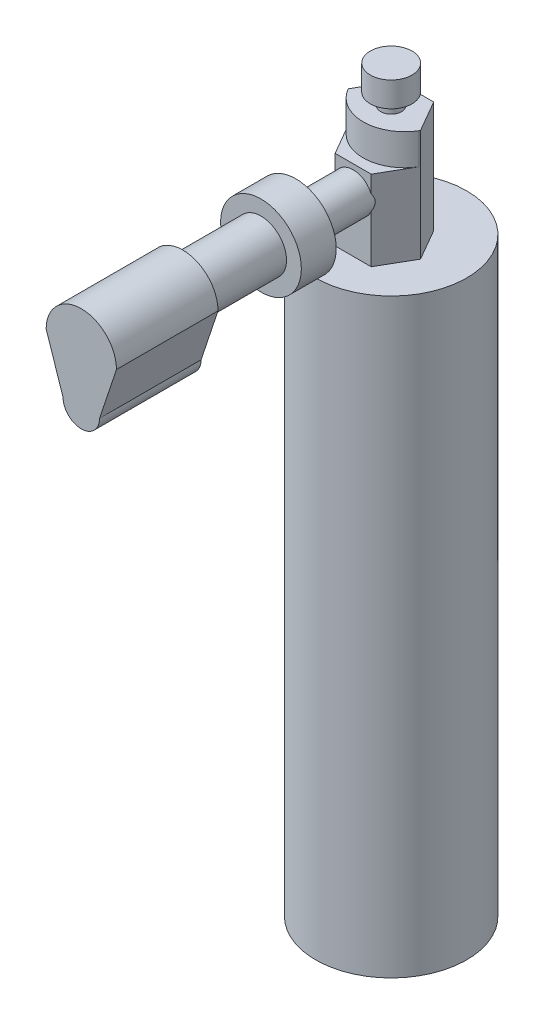
SolidWorks part; units mm, degrees
ref_plane "Front Plane" through (0, 0, 0) normal (0, 0, 1) x (1, 0, 0)
ref_plane "Top Plane" through (0, 0, 0) normal (0, 1, 0) x (1, 0, 0)
ref_plane "Right Plane" through (0, 0, 0) normal (1, 0, 0) x (0, 0, -1)
sketch "Sketch1" plane through (0, 0, 0) normal (0, 1, 0) x (1, 0, 0)
  circle A0 centre (0, 0) radius 14.5
  dimension "D1" = 29
extrude "Boss-Extrude1" add sketch "Sketch1" along normal blind 113.4
sketch "Sketch2" plane through (0, 113.4, 0) normal (0, 1, 0) x (1, 0, 0)
  circle A0 centre (0, 0) radius 2
  dimension "D1" = 4
extrude "Boss-Extrude2" add sketch "Sketch2" along normal blind 28.5
sketch "Sketch3" plane through (0, 141.9, 0) normal (0, 1, 0) x (1, 0, 0)
  circle A0 centre (0, 0) radius 4
  dimension "D1" = 8
extrude "Boss-Extrude3" add sketch "Sketch3" against normal blind 4.8
sketch "Sketch4" plane through (0, 113.4, 0) normal (0, 1, 0) x (1, 0, 0)
  line L3 (3.4641, 4.7) -> (-3.4641, 4.7)
  line L4 (-3.4641, 4.7) -> (-6.9282, -1.3)
  line L5 (-6.9282, -1.3) -> (-3.4641, -7.3)
  line L6 (-3.4641, -7.3) -> (3.4641, -7.3)
  line L7 (3.4641, -7.3) -> (6.9282, -1.3)
  line L8 (6.9282, -1.3) -> (3.4641, 4.7)
  circle A0 centre (0, 0) radius 14.5 construction
  circle A1 centre (0, -1.3) radius 6.9282 construction
  circle A4 centre (0, 0) radius 14.5 construction
  dimension "D1" = 12
  dimension "D2" = 4.7
extrude "Boss-Extrude4" add sketch "Sketch4" along normal blind 21.4
sketch "Sketch6" plane through (0, 134.8, 0) normal (0, 1, 0) x (1, 0, 0)
  line L4 (-6.9282, -1.3) -> (-6.9282, -9.4658)
  line L5 (-6.9282, -9.4658) -> (6.9282, -9.4658)
  line L6 (6.9282, -1.3) -> (6.9282, -9.4658)
  arc A0 (-6.9282, -1.3) -> (6.9282, -1.3) centre (0, 2.5618) ccw
extrude "Cut-Extrude1" cut sketch "Sketch6" against normal blind 6
sketch "Sketch7" plane through (0, 0, 7.3) normal (0, 0, 1) x (1, 0, 0)
  line L0 (-3.4641, 128.8) -> (3.4641, 128.8) construction
  circle A0 centre (0, 124.05) radius 3.75
  dimension "D1" = 7.5
  dimension "D2" = 4.75
extrude "Boss-Extrude5" add sketch "Sketch7" along normal blind 11 and the other way blind 2
sketch "Sketch8" plane through (0, 0, 18.3) normal (0, 0, 1) x (1, 0, 0)
  circle A0 centre (0, 124.05) radius 7.75
  dimension "D1" = 15.5
extrude "Boss-Extrude6" add sketch "Sketch8" along normal blind 6.7
sketch "Sketch9" plane through (0, 0, 25) normal (0, 0, 1) x (1, 0, 0)
  circle A0 centre (0, 124.05) radius 4.9
  dimension "D1" = 9.8
extrude "Boss-Extrude7" add sketch "Sketch9" along normal blind 15
sketch "Sketch10" plane through (0, 0, 40) normal (0, 0, 1) x (1, 0, 0)
  line L0 (0, 117.8) -> (0, 110.8) construction
  line L1 (-6.75, 124.05) -> (-3.5, 114.3)
  line L2 (3.5, 114.3) -> (6.75, 124.05)
  arc A0 (6.75, 124.05) -> (-6.75, 124.05) centre (0, 124.05) ccw
  arc A1 (-3.5, 114.3) -> (3.5, 114.3) centre (0, 114.3) ccw
  dimension "D1" = 13.5
  dimension "D2" = 7
extrude "Boss-Extrude8" add sketch "Sketch10" along normal blind 19.5
sketch "Sketch11" plane through (0, 141.9, 0) normal (0, 1, 0) x (1, 0, 0)
  line L0 (0, 4) -> (0.2732, 3.6147)
  line L1 (0, 4) -> (0, 3.625) construction
  line L2 (0, 4) -> (-0.2732, 3.6147)
  line L3 (0.6106, 3.9531) -> (0.8217, 3.5306)
  line L4 (0.6106, 3.9531) -> (0.2818, 3.614)
  line L5 (1.2069, 3.8136) -> (1.351, 3.3638)
  line L6 (1.2069, 3.8136) -> (0.8302, 3.5287)
  line L7 (1.7749, 3.5847) -> (1.8487, 3.1182)
  line L8 (1.7749, 3.5847) -> (1.3591, 3.3606)
  line L9 (2.3013, 3.2717) -> (2.303, 2.7994)
  line L10 (2.3013, 3.2717) -> (1.8562, 3.1137)
  line L11 (2.7737, 2.8821) -> (2.7034, 2.4151)
  line L12 (2.7737, 2.8821) -> (2.3097, 2.7939)
  line L13 (3.1812, 2.4249) -> (3.0403, 1.9741)
  line L14 (3.1812, 2.4249) -> (2.7091, 2.4086)
  line L15 (3.514, 1.9109) -> (3.306, 1.4868)
  line L16 (3.514, 1.9109) -> (3.0451, 1.9668)
  line L17 (3.7646, 1.3521) -> (3.4943, 0.9648)
  line L18 (3.7646, 1.3521) -> (3.3096, 1.4789)
  line L19 (3.9268, 0.7616) -> (3.6006, 0.4201)
  line L20 (3.9268, 0.7616) -> (3.4966, 0.9564)
  line L21 (3.9971, 0.1532) -> (3.6225, -0.1345)
  line L22 (3.9971, 0.1532) -> (3.6016, 0.4114)
  line L23 (3.9736, -0.4587) -> (3.5595, -0.6859)
  line L24 (3.9736, -0.4587) -> (3.6222, -0.1432)
  line L25 (3.857, -1.0599) -> (3.4131, -1.2212)
  line L26 (3.857, -1.0599) -> (3.5579, -0.6944)
  line L27 (3.65, -1.6363) -> (3.1867, -1.7279)
  line L28 (3.65, -1.6363) -> (3.4102, -1.2294)
  line L29 (3.3575, -2.1743) -> (2.8856, -2.1941)
  line L30 (3.3575, -2.1743) -> (3.1825, -1.7356)
  line L31 (2.9862, -2.6613) -> (2.5168, -2.6089)
  line L32 (2.9862, -2.6613) -> (2.8803, -2.201)
  line L33 (2.545, -3.086) -> (2.0891, -2.9625)
  line L34 (2.545, -3.086) -> (2.5106, -2.6149)
  line L35 (2.0441, -3.4383) -> (1.6124, -3.2467)
  line L36 (2.0441, -3.4383) -> (2.082, -2.9675)
  line L37 (1.4953, -3.71) -> (1.0979, -3.4547)
  line L38 (1.4953, -3.71) -> (1.6046, -3.2505)
  line L39 (0.9114, -3.8948) -> (0.5577, -3.5818)
  line L40 (0.9114, -3.8948) -> (1.0896, -3.4574)
  line L41 (0.3062, -3.9883) -> (0.0044, -3.625)
  line L42 (0.3062, -3.9883) -> (0.5491, -3.5832)
  line L43 (-0.3062, -3.9883) -> (-0.5491, -3.5832)
  line L44 (-0.3062, -3.9883) -> (-0.0044, -3.625)
  line L45 (-0.9114, -3.8948) -> (-1.0896, -3.4574)
  line L46 (-0.9114, -3.8948) -> (-0.5577, -3.5818)
  line L47 (-1.4953, -3.71) -> (-1.6046, -3.2505)
  line L48 (-1.4953, -3.71) -> (-1.0979, -3.4547)
  line L49 (-2.0441, -3.4383) -> (-2.082, -2.9675)
  line L50 (-2.0441, -3.4383) -> (-1.6124, -3.2467)
  line L51 (-2.545, -3.086) -> (-2.5106, -2.6149)
  line L52 (-2.545, -3.086) -> (-2.0891, -2.9625)
  line L53 (-2.9862, -2.6613) -> (-2.8803, -2.201)
  line L54 (-2.9862, -2.6613) -> (-2.5168, -2.6089)
  line L55 (-3.3575, -2.1743) -> (-3.1825, -1.7356)
  line L56 (-3.3575, -2.1743) -> (-2.8856, -2.1941)
  line L57 (-3.65, -1.6363) -> (-3.4102, -1.2294)
  line L58 (-3.65, -1.6363) -> (-3.1867, -1.7279)
  line L59 (-3.857, -1.0599) -> (-3.5579, -0.6944)
  line L60 (-3.857, -1.0599) -> (-3.4131, -1.2212)
  line L61 (-3.9736, -0.4587) -> (-3.6222, -0.1432)
  line L62 (-3.9736, -0.4587) -> (-3.5595, -0.6859)
  line L63 (-3.9971, 0.1532) -> (-3.6016, 0.4114)
  line L64 (-3.9971, 0.1532) -> (-3.6225, -0.1345)
  line L65 (-3.9268, 0.7616) -> (-3.4966, 0.9564)
  line L66 (-3.9268, 0.7616) -> (-3.6006, 0.4201)
  line L67 (-3.7646, 1.3521) -> (-3.3096, 1.4789)
  line L68 (-3.7646, 1.3521) -> (-3.4943, 0.9648)
  line L69 (-3.514, 1.9109) -> (-3.0451, 1.9668)
  line L70 (-3.514, 1.9109) -> (-3.306, 1.4868)
  line L71 (-3.1812, 2.4249) -> (-2.7091, 2.4086)
  line L72 (-3.1812, 2.4249) -> (-3.0403, 1.9741)
  line L73 (-2.7737, 2.8821) -> (-2.3097, 2.7939)
  line L74 (-2.7737, 2.8821) -> (-2.7034, 2.4151)
  line L75 (-2.3013, 3.2717) -> (-1.8562, 3.1137)
  line L76 (-2.3013, 3.2717) -> (-2.303, 2.7994)
  line L77 (-1.7749, 3.5847) -> (-1.3591, 3.3606)
  line L78 (-1.7749, 3.5847) -> (-1.8487, 3.1182)
  line L79 (-1.2069, 3.8136) -> (-0.8302, 3.5287)
  line L80 (-1.2069, 3.8136) -> (-1.351, 3.3638)
  line L81 (-0.6106, 3.9531) -> (-0.2818, 3.614)
  line L82 (-0.6106, 3.9531) -> (-0.8217, 3.5306)
  arc A0 (-0.2732, 3.6147) -> (-0.2818, 3.614) centre (0, 0) ccw construction
  circle A1 centre (0, 0) radius 4 construction
  circle A2 centre (0, 0) radius 4
  arc A3 (0.2818, 3.614) -> (0.2732, 3.6147) centre (0, 0) ccw
  arc A4 (0.2818, 3.614) -> (0.2732, 3.6147) centre (0, 0) ccw construction
  arc A5 (0.8302, 3.5287) -> (0.8217, 3.5306) centre (0, 0) ccw construction
  arc A6 (0.8302, 3.5287) -> (0.8217, 3.5306) centre (0, 0) ccw
  arc A7 (1.3591, 3.3606) -> (1.351, 3.3638) centre (0, 0) ccw construction
  arc A8 (1.3591, 3.3606) -> (1.351, 3.3638) centre (0, 0) ccw
  arc A9 (-0.2732, 3.6147) -> (-0.2818, 3.614) centre (0, 0) ccw
  arc A10 (-0.8217, 3.5306) -> (-0.8302, 3.5287) centre (0, 0) ccw construction
  arc A11 (-0.8217, 3.5306) -> (-0.8302, 3.5287) centre (0, 0) ccw
  arc A12 (-1.351, 3.3638) -> (-1.3591, 3.3606) centre (0, 0) ccw construction
  arc A13 (-1.351, 3.3638) -> (-1.3591, 3.3606) centre (0, 0) ccw
  arc A14 (-1.8487, 3.1182) -> (-1.8562, 3.1137) centre (0, 0) ccw construction
  arc A15 (-1.8487, 3.1182) -> (-1.8562, 3.1137) centre (0, 0) ccw
  arc A16 (1.8562, 3.1137) -> (1.8487, 3.1182) centre (0, 0) ccw construction
  arc A17 (1.8562, 3.1137) -> (1.8487, 3.1182) centre (0, 0) ccw
  arc A18 (2.3097, 2.7939) -> (2.303, 2.7994) centre (0, 0) ccw construction
  arc A19 (2.3097, 2.7939) -> (2.303, 2.7994) centre (0, 0) ccw
  arc A20 (2.7091, 2.4086) -> (2.7034, 2.4151) centre (0, 0) ccw construction
  arc A21 (2.7091, 2.4086) -> (2.7034, 2.4151) centre (0, 0) ccw
  arc A22 (3.0451, 1.9668) -> (3.0403, 1.9741) centre (0, 0) ccw construction
  arc A23 (3.0451, 1.9668) -> (3.0403, 1.9741) centre (0, 0) ccw
  arc A24 (3.3096, 1.4789) -> (3.306, 1.4868) centre (0, 0) ccw construction
  arc A25 (3.3096, 1.4789) -> (3.306, 1.4868) centre (0, 0) ccw
  arc A26 (3.4966, 0.9564) -> (3.4943, 0.9648) centre (0, 0) ccw construction
  arc A27 (3.4966, 0.9564) -> (3.4943, 0.9648) centre (0, 0) ccw
  arc A28 (3.6016, 0.4114) -> (3.6006, 0.4201) centre (0, 0) ccw construction
  arc A29 (3.6016, 0.4114) -> (3.6006, 0.4201) centre (0, 0) ccw
  arc A30 (3.6222, -0.1432) -> (3.6225, -0.1345) centre (0, 0) ccw construction
  arc A31 (3.6222, -0.1432) -> (3.6225, -0.1345) centre (0, 0) ccw
  arc A32 (3.5579, -0.6944) -> (3.5595, -0.6859) centre (0, 0) ccw construction
  arc A33 (3.5579, -0.6944) -> (3.5595, -0.6859) centre (0, 0) ccw
  arc A34 (3.4102, -1.2294) -> (3.4131, -1.2212) centre (0, 0) ccw construction
  arc A35 (3.4102, -1.2294) -> (3.4131, -1.2212) centre (0, 0) ccw
  arc A36 (3.1825, -1.7356) -> (3.1867, -1.7279) centre (0, 0) ccw construction
  arc A37 (3.1825, -1.7356) -> (3.1867, -1.7279) centre (0, 0) ccw
  arc A38 (2.8803, -2.201) -> (2.8856, -2.1941) centre (0, 0) ccw construction
  arc A39 (2.8803, -2.201) -> (2.8856, -2.1941) centre (0, 0) ccw
  arc A40 (2.5106, -2.6149) -> (2.5168, -2.6089) centre (0, 0) ccw construction
  arc A41 (2.5106, -2.6149) -> (2.5168, -2.6089) centre (0, 0) ccw
  arc A42 (2.082, -2.9675) -> (2.0891, -2.9625) centre (0, 0) ccw construction
  arc A43 (2.082, -2.9675) -> (2.0891, -2.9625) centre (0, 0) ccw
  arc A44 (1.6046, -3.2505) -> (1.6124, -3.2467) centre (0, 0) ccw construction
  arc A45 (1.6046, -3.2505) -> (1.6124, -3.2467) centre (0, 0) ccw
  arc A46 (1.0896, -3.4574) -> (1.0979, -3.4547) centre (0, 0) ccw construction
  arc A47 (1.0896, -3.4574) -> (1.0979, -3.4547) centre (0, 0) ccw
  arc A48 (0.5491, -3.5832) -> (0.5577, -3.5818) centre (0, 0) ccw construction
  arc A49 (0.5491, -3.5832) -> (0.5577, -3.5818) centre (0, 0) ccw
  arc A50 (-0.0044, -3.625) -> (0.0044, -3.625) centre (0, 0) ccw construction
  arc A51 (-0.5577, -3.5818) -> (-0.5491, -3.5832) centre (0, 0) ccw construction
  arc A52 (-0.5577, -3.5818) -> (-0.5491, -3.5832) centre (0, 0) ccw
  arc A53 (-0.0044, -3.625) -> (0.0044, -3.625) centre (0, 0) ccw
  arc A54 (-1.0979, -3.4547) -> (-1.0896, -3.4574) centre (0, 0) ccw construction
  arc A55 (-1.0979, -3.4547) -> (-1.0896, -3.4574) centre (0, 0) ccw
  arc A56 (-1.6124, -3.2467) -> (-1.6046, -3.2505) centre (0, 0) ccw construction
  arc A57 (-1.6124, -3.2467) -> (-1.6046, -3.2505) centre (0, 0) ccw
  arc A58 (-2.0891, -2.9625) -> (-2.082, -2.9675) centre (0, 0) ccw construction
  arc A59 (-2.0891, -2.9625) -> (-2.082, -2.9675) centre (0, 0) ccw
  arc A60 (-2.5168, -2.6089) -> (-2.5106, -2.6149) centre (0, 0) ccw construction
  arc A61 (-2.5168, -2.6089) -> (-2.5106, -2.6149) centre (0, 0) ccw
  arc A62 (-2.8856, -2.1941) -> (-2.8803, -2.201) centre (0, 0) ccw construction
  arc A63 (-2.8856, -2.1941) -> (-2.8803, -2.201) centre (0, 0) ccw
  arc A64 (-3.1867, -1.7279) -> (-3.1825, -1.7356) centre (0, 0) ccw construction
  arc A65 (-3.1867, -1.7279) -> (-3.1825, -1.7356) centre (0, 0) ccw
  arc A66 (-3.4131, -1.2212) -> (-3.4102, -1.2294) centre (0, 0) ccw construction
  arc A67 (-3.4131, -1.2212) -> (-3.4102, -1.2294) centre (0, 0) ccw
  arc A68 (-3.5595, -0.6859) -> (-3.5579, -0.6944) centre (0, 0) ccw construction
  arc A69 (-3.5595, -0.6859) -> (-3.5579, -0.6944) centre (0, 0) ccw
  arc A70 (-3.6225, -0.1345) -> (-3.6222, -0.1432) centre (0, 0) ccw construction
  arc A71 (-3.6225, -0.1345) -> (-3.6222, -0.1432) centre (0, 0) ccw
  arc A72 (-3.6006, 0.4201) -> (-3.6016, 0.4114) centre (0, 0) ccw construction
  arc A73 (-3.6006, 0.4201) -> (-3.6016, 0.4114) centre (0, 0) ccw
  arc A74 (-3.4943, 0.9648) -> (-3.4966, 0.9564) centre (0, 0) ccw construction
  arc A75 (-3.4943, 0.9648) -> (-3.4966, 0.9564) centre (0, 0) ccw
  arc A76 (-3.306, 1.4868) -> (-3.3096, 1.4789) centre (0, 0) ccw construction
  arc A77 (-3.0403, 1.9741) -> (-3.0451, 1.9668) centre (0, 0) ccw construction
  arc A78 (-3.0403, 1.9741) -> (-3.0451, 1.9668) centre (0, 0) ccw
  arc A79 (-2.7034, 2.4151) -> (-2.7091, 2.4086) centre (0, 0) ccw construction
  arc A80 (-2.7034, 2.4151) -> (-2.7091, 2.4086) centre (0, 0) ccw
  arc A81 (-2.303, 2.7994) -> (-2.3097, 2.7939) centre (0, 0) ccw construction
  arc A82 (-2.303, 2.7994) -> (-2.3097, 2.7939) centre (0, 0) ccw
  arc A83 (-3.306, 1.4868) -> (-3.3096, 1.4789) centre (0, 0) ccw
  point P132 (0, 0)
  circle M1 centre (0, 0) radius 4
  dimension "D1" = 7.25
  dimension "D2" = 41
extrude "Cut-Extrude2" [suppressed] cut sketch "Sketch11" against normal up to surface (4.8 mm away) contours A3 L4 L0 M1 | A6 L6 L3 M1 | A8 L8 L5 M1 | A17 L10 L7 M1 | A19 L12 L9 M1 | A21 L14 L11 M1 | A23 L16 L13 M1 | A25 L18 L15 M1 | A27 L20 L17 M1 | A29 L22 L19 M1 | A31 L24 L21 M1 | A33 L26 L23 M1 | A35 L28 L25 M1 | A37 L30 L27 M1 | A39 L32 L29 M1 | A43 L36 L33 M1 | A41 L34 L31 M1 | A45 L38 L35 M1 | A47 L40 L37 M1 | A49 L42 L39 M1 | A53 L44 L41 M1 | A52 L46 L43 M1 | A55 L48 L45 M1 | A57 L50 L47 M1 | A59 L52 L49 M1 | A61 L54 L51 M1 | A63 L56 L53 M1 | A65 L58 L55 M1 | A67 L60 L57 M1 | A69 L62 L59 M1 | A71 L64 L61 M1 | A73 L66 L63 M1 | A75 L68 L65 M1 | A83 L70 L67 M1 | A78 L72 L69 M1 | A80 L74 L71 M1 | A9 L2 L81 M1 | A11 L82 L79 M1 | A13 L80 L77 M1 | A15 L78 L75 M1 | A82 L76 L73 M1 up to face at (0, 137.1, 4)
